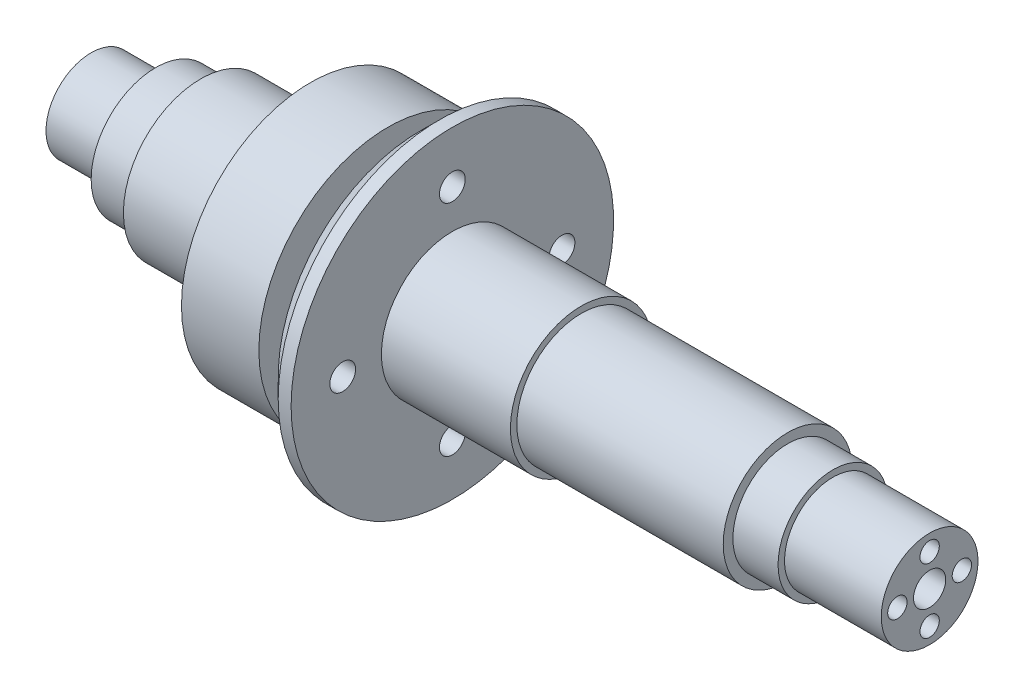
SolidWorks part; units mm, degrees
ref_plane "Front Plane" through (0, 0, 0) normal (0, 0, 1) x (1, 0, 0)
ref_plane "Top Plane" through (0, 0, 0) normal (0, 1, 0) x (1, 0, 0)
ref_plane "Right Plane" through (0, 0, 0) normal (1, 0, 0) x (0, 0, -1)
other "Center of Mass"
sketch "Sketch3" plane through (0, 0, 0) normal (0, 0, 1) x (1, 0, 0)
  line L0 (0, 0) -> (0, 39.0464) construction
  line L1 (-72.5, 0) -> (72.5, 0) construction
  line L2 (-72.5, 2.5) -> (-72.5, 0) construction
  line L3 (-72.5, 2.5) -> (-72.5, 7)
  line L4 (-72.5, 7) -> (-62.5, 7)
  line L5 (-62.5, 7) -> (-62.5, 10)
  line L6 (-62.5, 10) -> (-55.5, 10)
  line L7 (-55.5, 10) -> (-55.5, 12)
  line L8 (-55.5, 12) -> (-38.5, 12)
  line L9 (-38.5, 12) -> (-38.5, 20)
  line L10 (-38.5, 20) -> (-26.5, 20)
  line L11 (-26.5, 20) -> (-26.5, 11)
  line L12 (-26.5, 11) -> (-21.5, 11)
  line L13 (3.5, 11) -> (3.5, 10)
  line L14 (3.5, 10) -> (35.5, 10)
  line L15 (35.5, 10) -> (35.5, 8.5)
  line L17 (72.5, 7.5) -> (72.5, 2.5)
  line L18 (72.5, 2.5) -> (-72.5, 2.5)
  line L19 (-32.5, 20) -> (-32.5, 2.5) construction
  line L20 (-11.5, 11) -> (-11.5, 2.5) construction
  line L21 (-77.5, 12) -> (-72.8417, 12) construction
  line L22 (-62.5, 10) -> (-62.5, 16) construction
  line L23 (-77.5, 15) -> (-72.8417, 15) construction
  line L24 (35.5, 8.5) -> (42.5, 8.5)
  line L25 (11.9511, 11) -> (20.8732, 11) construction
  line L26 (30.861, 12) -> (33.3773, 12) construction
  line L27 (42.5, 8.5) -> (42.5, 7.5)
  line L36 (42.5, 7.5) -> (72.5, 7.5)
  line L37 (-21.5, 11) -> (-21.5, 25)
  line L38 (35.5, 8.5) -> (44.5, 8.5) construction
  line L39 (-21.5, 25) -> (-16.5, 25)
  line L40 (-16.5, 25) -> (-16.5, 11)
  line L42 (-16.5, 11) -> (3.5, 11)
  point P5 (0, 0)
  dimension "D3" = 40
  dimension "D2" = 22
  dimension "D4" = 40
  dimension "D5" = 12
  dimension "D6" = 10
  dimension "D7" = 7
  dimension "D9" = 5
  dimension "D10" = 14
  dimension "D11" = 20
  dimension "D12" = 12
  dimension "D13" = 24
  dimension "D14" = 32
  dimension "D15" = 15
  dimension "D16" = 20
  dimension "D18" = 11
  dimension "D20" = 12
  dimension "D21" = 7
  dimension "D22" = 17
  dimension "D24" = 15
  dimension "D8" = 30
  dimension "D17" = 32
  dimension "D19" = 30
  dimension "D23" = 5
  dimension "D25" = 5
  dimension "D26" = 25
revolve "Revolve1" add sketch "Sketch3" angle 360 about L1
ref_plane "Plane1" through (0, 11, 0) normal (0, 1, 0) x (1, 0, 0)
sketch "Sketch4" plane through (0, 11, 0) normal (0, 1, 0) x (1, 0, 0)
  line L0 (3.5, 0) -> (-26.5, 0) construction
  line L1 (3.5, -11) -> (3.5, 11) construction
  line L2 (-26.5, -11) -> (-26.5, 11) construction
  line L3 (-11.5, 0) -> (-11.5, 23.5234) construction
  line L4 (72.5, -7.5) -> (72.5, 7.5) construction
  line L5 (72.5, 0) -> (62.5, 0) construction
  line L6 (-17.5, -2) -> (-5.5, -2)
  line L7 (-17.5, -2) -> (-17.5, 2)
  line L8 (-17.5, 2) -> (-5.5, 2)
  line L9 (-5.5, -2) -> (-5.5, 2)
  line L10 (-17.5, -2) -> (-5.5, 2) construction
  line L11 (-17.5, 2) -> (-5.5, -2) construction
  line L16 (56.5, -2) -> (68.5, -2)
  line L17 (56.5, -2) -> (56.5, 2)
  line L18 (56.5, 2) -> (68.5, 2)
  line L19 (68.5, -2) -> (68.5, 2)
  line L20 (56.5, -2) -> (68.5, 2) construction
  line L21 (56.5, 2) -> (68.5, -2) construction
  point P17 (62.5, 0)
  dimension "D1" = 12
  dimension "D2" = 4
  dimension "D3" = 10
  dimension "D4" = 12
  dimension "D5" = 4
fillet "Fillet1" radius 1 2 edges at (-26.5, 0, 11) (-38.5, 0, 12)
ref_plane "Plane2" through (0, 7.5, 0) normal (0, 1, 0) x (1, 0, 0)
sketch "Sketch5" plane through (0, 7.5, 0) normal (0, 1, 0) x (1, 0, 0)
  line L0 (68.5, -2) -> (68.5, 2) construction
  line L1 (56.5, -2) -> (68.5, -2) construction
  line L2 (56.5, -2) -> (56.5, 2) construction
  line L3 (56.5, 2) -> (68.5, 2) construction
  line L4 (68.5, -2) -> (68.5, 2)
  line L5 (56.5, -2) -> (68.5, -2)
  line L6 (56.5, -2) -> (56.5, 2)
  line L7 (56.5, 2) -> (68.5, 2)
sketch "Sketch6" [suppressed] plane through (0, 0, 0) normal (0, 0, 1) x (1, 0, 0)
  line L0 (-52.75, 0) -> (52.75, 0) construction
  line L1 (-52.75, 4.5) -> (-52.75, 7)
  line L2 (-52.75, 7) -> (-42.75, 7)
  line L3 (-42.75, 7) -> (-42.75, 10)
  line L4 (-42.75, 10) -> (-35.75, 10)
  line L5 (-35.75, 10) -> (-35.75, 12)
  line L6 (-35.75, 12) -> (-28.25, 12)
  line L7 (-28.25, 12) -> (-28.25, 11)
  line L8 (-28.25, 11) -> (-1.75, 11)
  line L9 (44.75, 11) -> (44.75, 8.5)
  line L10 (44.75, 8.5) -> (52.75, 8.5)
  line L11 (52.75, 8.5) -> (52.75, 4.5)
  line L12 (52.75, 4.5) -> (-52.75, 4.5)
  line L13 (8.25, 11) -> (8.25, 4.5) construction
  line L14 (-1.75, 11) -> (-1.75, 22)
  line L15 (-1.75, 22) -> (3.25, 22)
  line L16 (3.25, 22) -> (3.25, 11)
  line L17 (3.25, 11) -> (44.75, 11)
  point P4 (0, 0)
  dimension "D1" = 10
  dimension "D2" = 7
  dimension "D3" = 8
  dimension "D4" = 61
  dimension "D5" = 105.5
  dimension "D6" = 7
  dimension "D7" = 10
  dimension "D8" = 12
  dimension "D9" = 11
  dimension "D10" = 8.5
  dimension "D11" = 9
  dimension "D12" = 31.5
  dimension "D13" = 5
  dimension "D14" = 22
  dimension "D15" = 24.5
revolve "Revolve2" [suppressed] add sketch "Sketch6" angle 360 about L0
ref_plane "Plane3" [suppressed] through (0, 11, 0) normal (0, 1, 0) x (1, 0, 0)
sketch "Sketch8" plane through (-16.5, 0, 0) normal (1, 0, 0) x (0, 0, -1)
  line L0 (0, 0) -> (0, 17) construction
  circle A0 centre (0, 17) radius 2
  circle A1 centre (17, 0) radius 2
  circle A2 centre (0, -17) radius 2
  circle A3 centre (-17, 0) radius 2
  point P12 (0, 0)
  dimension "D1" = 4
  dimension "D3" = 17
  dimension "D4" = 17
  dimension "D5" = 34
  dimension "D2" = 4
extrude "Cut-Extrude5" cut sketch "Sketch8" against normal up to surface (5 mm away) up to face at (-21.5, 0, 11)
sketch "Sketch9" [suppressed] plane through (3.25, 0, 0) normal (1, 0, 0) x (0, 0, -1)
  line L0 (0, 0) -> (0, 17) construction
  circle A0 centre (0, 17) radius 2
  circle A1 centre (17, 0) radius 2
  circle A2 centre (0, -17) radius 2
  circle A3 centre (-17, 0) radius 2
  point P12 (0, 0)
  dimension "D1" = 4
  dimension "D2" = 17
  dimension "D4" = 17
  dimension "D5" = 17
  dimension "D3" = 4
extrude "Cut-Extrude6" [suppressed] cut sketch "Sketch9" against normal up to surface (5 mm away)
sketch "Sketch10" plane through (72.5, 0, 0) normal (1, 0, 0) x (0, 0, -1)
  circle A1 centre (0, 0) radius 7.5 construction
  circle A2 centre (0, 0) radius 7.5
extrude "Cut-Extrude7" cut sketch "Sketch10" against normal blind 15
sketch "Sketch11" plane through (57.5, 0, 0) normal (1, 0, 0) x (0, 0, -1)
  line L0 (0, 0) -> (0, 5) construction
  circle A0 centre (0, 5) radius 1.5
  circle A1 centre (5, 0) radius 1.5
  circle A2 centre (0, -5) radius 1.5
  circle A3 centre (-5, 0) radius 1.5
  point P12 (0, 0)
  dimension "D1" = 3
  dimension "D3" = 5
  dimension "D2" = 4
extrude "Cut-Extrude8" cut sketch "Sketch11" against normal blind 10
chamfer "Chamfer1" distance 3 angle 45 1 edges at (-21.5, 0, 25)
equation "\"mainShaft-D\"= 20mm"
equation "\"mainTrackGear-D\"= 40mm"
equation "\"D4@Sketch3\"=\"wormGearL-D\""
equation "\"D11@Sketch3\"=\"mainShaft-D\""
equation "\"mini-flipper-shaft-diameter\"= 26mm"
equation "\"mini-shaft-ring-groove-diam\"= 7.8mm"
equation "\"mini-shaft-ring-groove-width\"= 1mm"
equation "\"dtCoverPlate-DistFrom-GearCent\"= 73mm"
equation "\"wormGearShaft-L\"= \"dtCoverPlate-DistFrom-GearCent\" - 27.75 + 3.75"
equation "\"wormGearShaft-Dsmall\"= 6mm"
equation "\"wormGearShaft-Dworm\"= 12mm"
equation "\"wormL-D\" = 12mm"
equation "\"wormR-D\" = 15mm"
equation "\"wormGearL-D\" = 40mm"
equation "\"wormGearR-D\" = 50mm"
